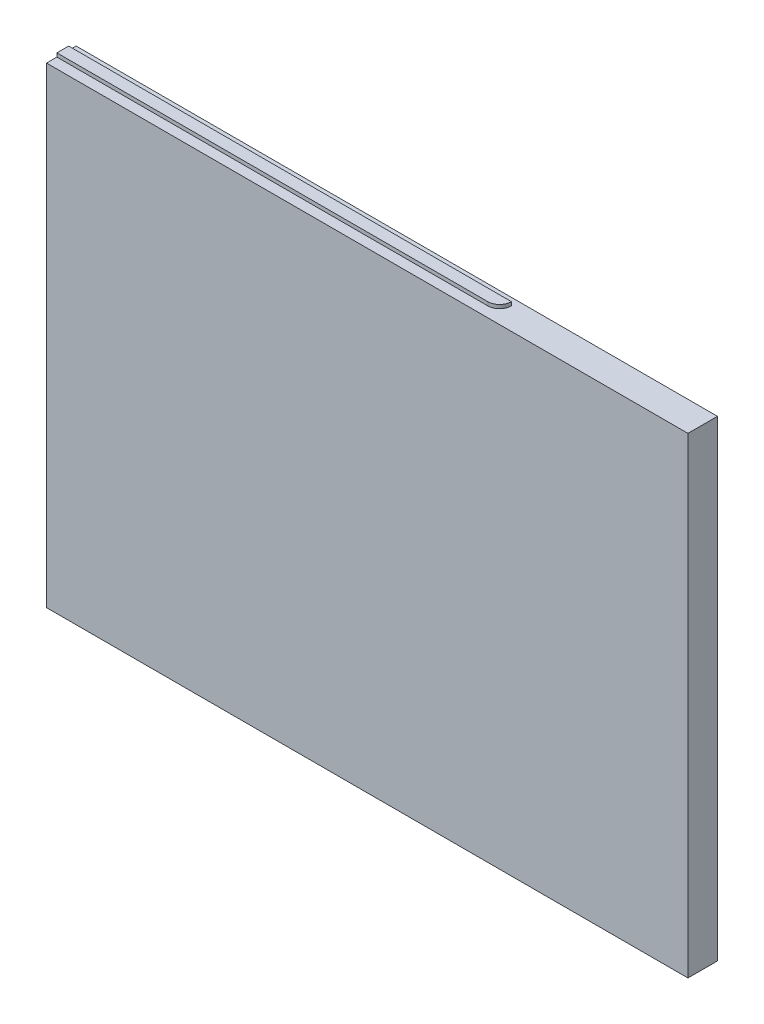
SolidWorks part; units mm, degrees
ref_plane "Plano frontal" through (0, 0, 0) normal (0, 0, 1) x (1, 0, 0)
ref_plane "Plano superior" through (0, 0, 0) normal (0, 1, 0) x (1, 0, 0)
ref_plane "Plano direito" through (0, 0, 0) normal (1, 0, 0) x (0, 0, -1)
sketch "Esboço1" plane through (0, 0, 0) normal (0, 0, 1) x (1, 0, 0)
  line L1 (-67.1292, 37.0793) -> (150.1708, 37.0793)
  line L2 (-67.1292, 37.0793) -> (-67.1292, -122.7207)
  line L3 (-67.1292, -122.7207) -> (150.1708, -122.7207)
  line L4 (150.1708, 37.0793) -> (150.1708, -122.7207)
  dimension "D1" = 217.3
  dimension "D2" = 159.8
extrude "Ressalto-extrusão1" add sketch "Esboço1" along normal blind 10
sketch "Esboço2" plane through (0, 37.0793, 0) normal (0, 1, 0) x (1, 0, 0)
  line L0 (-67.1292, -10) -> (-67.1292, 0) construction
  line L1 (-67.1292, -6.5) -> (82.8708, -6.5)
  line L2 (-67.1292, -6.5) -> (-67.1292, -2.5)
  line L3 (-67.1292, -2.5) -> (82.8708, -2.5)
  line L4 (82.8708, -6.5) -> (82.8708, -2.5)
  line L5 (150.1708, 0) -> (-67.1292, 0) construction
  dimension "D1" = 4
  dimension "D2" = 150
  dimension "D3" = 0
  dimension "D4" = 2.5
extrude "Ressalto-extrusão2" add sketch "Esboço2" along normal blind 1.24 and the other way blind 161.04 contours L1 L4 L3 L2
fillet "Filete1" radius 4 1 edges at (82.8708, -123.3407, 6.5)
ref_plane "Plano1" through (82.8708, -123.9607, 2.5) normal (0, 1, 0) x (1, 0, 0)
fillet "Filete2" radius 4 1 edges at (82.8708, 37.6993, 6.5)
